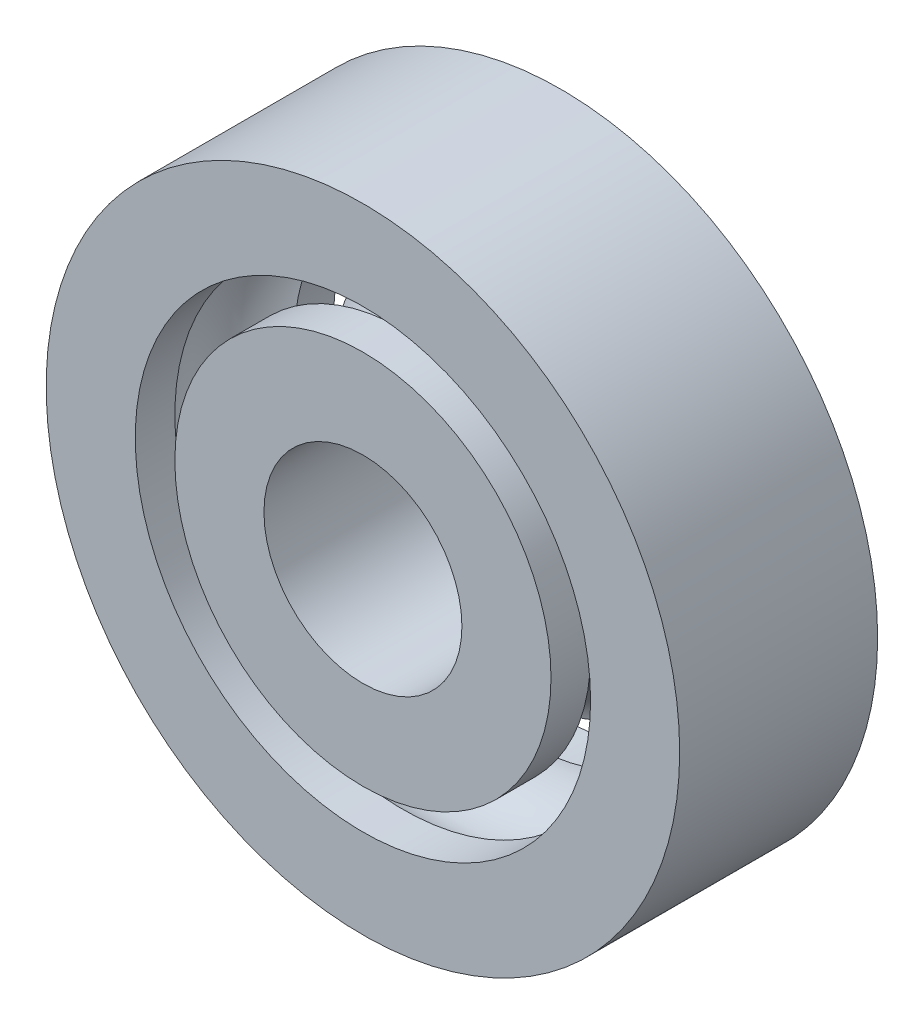
SolidWorks part; units mm, degrees
ref_plane "Front Plane" through (0, 0, 0) normal (0, 0, 1) x (1, 0, 0)
ref_plane "Top Plane" through (0, 0, 0) normal (0, 1, 0) x (1, 0, 0)
ref_plane "Right Plane" through (0, 0, 0) normal (1, 0, 0) x (0, 0, -1)
sketch "Sketch3" plane through (0, 0, 0) normal (1, 0, 0) x (0, 0, -1)
  line L0 (55, 0) -> (-55, 0) construction
  line L2 (-2.5, 2.5) -> (-2.5, 4.75)
  line L3 (-2.5, 8) -> (2.5, 8)
  line L4 (2.5, 2.5) -> (2.5, 4.75)
  line L5 (-2.5, 2.5) -> (2.5, 2.5)
  line L6 (0, 8) -> (0, 0) construction
  line L7 (0, 55) -> (0, -55) construction
  line L8 (-2.5, 0) -> (2.5, 0) construction
  line L9 (-2.5, 5.75) -> (-1.5, 5.75)
  line L10 (2.5, 5.75) -> (1.5, 5.75)
  line L11 (-2.5, 4.75) -> (-1.5, 4.75)
  line L12 (2.5, 4.75) -> (1.5, 4.75)
  line L13 (2.5, 5.75) -> (2.5, 8)
  line L14 (-2.5, 5.75) -> (-2.5, 8)
  arc A0 (-1.5, 5.75) -> (1.5, 5.75) centre (0, 5.25) cw
  arc A1 (-1.5, 4.75) -> (1.5, 4.75) centre (0, 5.25) ccw
  point P22 (0, 5.5282)
  dimension "D7" = 1.5811
  dimension "D1" = 2.5
  dimension "D2" = 8
  dimension "D3" = 5
  dimension "D4" = 1
  dimension "D5" = 2.25
  dimension "D6" = 2.25
revolve "Revolve1" add sketch "Sketch3" angle 360 about L8 region at (0, 3.4441, 0) region at (0, 7.0559, 0)
